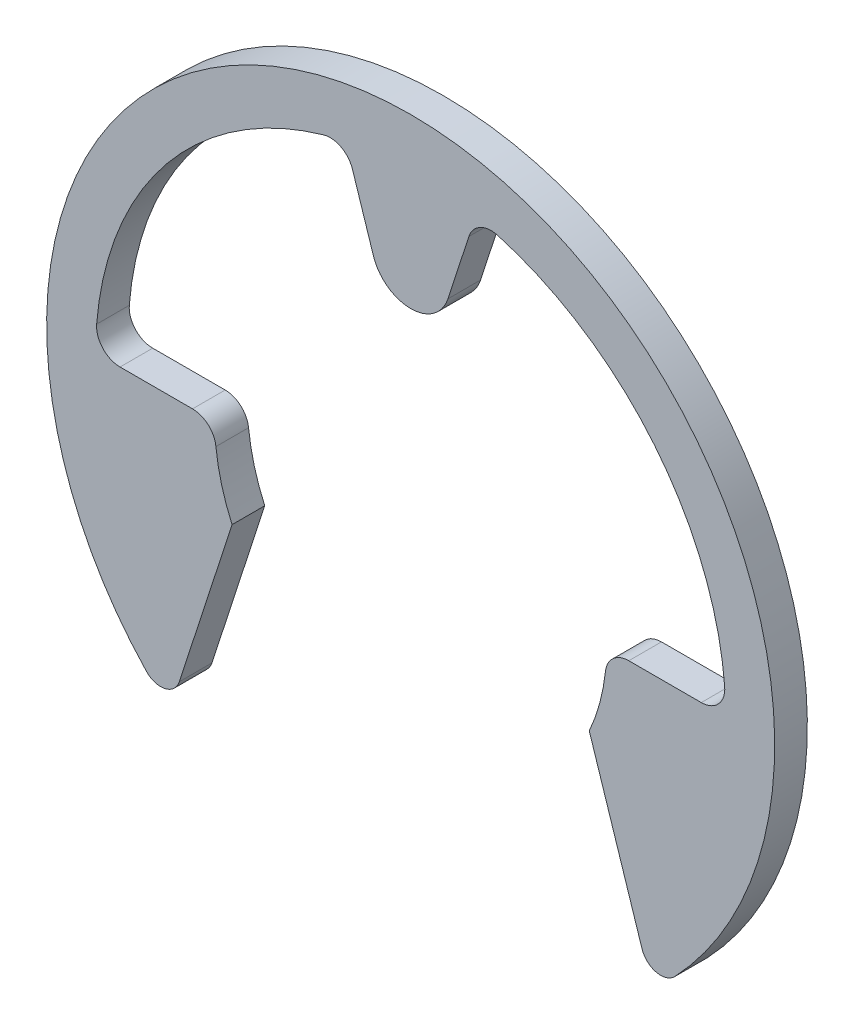
SolidWorks part; units mm, degrees
ref_plane "Front Plane" through (0, 0, 0) normal (0, 0, 1) x (1, 0, 0)
ref_plane "Top Plane" through (0, 0, 0) normal (0, 1, 0) x (1, 0, 0)
ref_plane "Right Plane" through (0, 0, 0) normal (1, 0, 0) x (0, 0, -1)
sketch "BodySke" plane through (0, 0, 0) normal (0, 0, 1) x (1, 0, 0)
  line L0 (-34.7902, 0) -> (37.4871, 0) construction
  line L1 (0, -29.1266) -> (0, 42.3415) construction
  line L2 (10.94, -4.9312) -> (14.1741, -14.8846)
  line L3 (-10.94, -4.9312) -> (-14.1741, -14.8846)
  line L4 (12, 0) -> (19.3, 0)
  line L5 (-12, 0) -> (-19.3, 0)
  line L6 (-1.7042, 11.8784) -> (-3.9808, 18.885) construction
  line L7 (1.7042, 11.8784) -> (3.9808, 18.885) construction
  line L8 (-2.2825, 13.6584) -> (-3.9808, 18.885)
  line L9 (2.2825, 13.6584) -> (3.9808, 18.885)
  arc A0 (16.1864, -15.3392) -> (-16.1864, -15.3392) centre (0, 0) ccw
  arc A1 (-12, 0) -> (-10.94, -4.9312) centre (0, 0) ccw
  arc A2 (-3.9808, 18.885) -> (-19.3, 0) centre (0, 0) ccw
  arc A3 (1.7042, 11.8784) -> (-1.7042, 11.8784) centre (0, 0) ccw construction
  circle A4 centre (0, 0) radius 19.3 construction
  circle A5 centre (0, 0) radius 22.3 construction
  arc A6 (10.94, -4.9312) -> (12, 0) centre (0, 0) ccw
  arc A7 (19.3, 0) -> (3.9808, 18.885) centre (0, 0) ccw
  arc A8 (-14.1741, -14.8846) -> (-16.1864, -15.3392) centre (-15.3153, -14.5138) cw
  arc A9 (16.1864, -15.3392) -> (14.1741, -14.8846) centre (15.3153, -14.5138) cw
  arc A10 (-2.2825, 13.6584) -> (2.2825, 13.6584) centre (0, 14.4) ccw
  point P23 (-14.7671, -16.7099)
  point P26 (14.7671, -16.7099)
  point P29 (-19.3, 0)
  point P32 (19.3, 0)
  point P35 (3.9808, 18.885)
  point P38 (-3.9808, 18.885)
  dimension "D1" = 4.8
  dimension "Angle" = 36
extrude "BaseBody" add sketch "BodySke" along normal blind 2
fillet "Fillet1" radius 1.44 6 edges at (19.3, 0, 1) (-19.3, 0, 1) (3.9808, 18.885, 1) (-3.9808, 18.885, 1) (12, 0, 1) (-12, 0, 1)
equation "\"D8@BodySke\" = \"Inside_Diameter@BodySke\" * 0.05"
equation "\"Fillet_radius@Fillet1\" = \"Inside_Diameter@BodySke\" * 0.06"
equation "\"D1@BodySke\" = \"Inside_Diameter@BodySke\" / 5"
